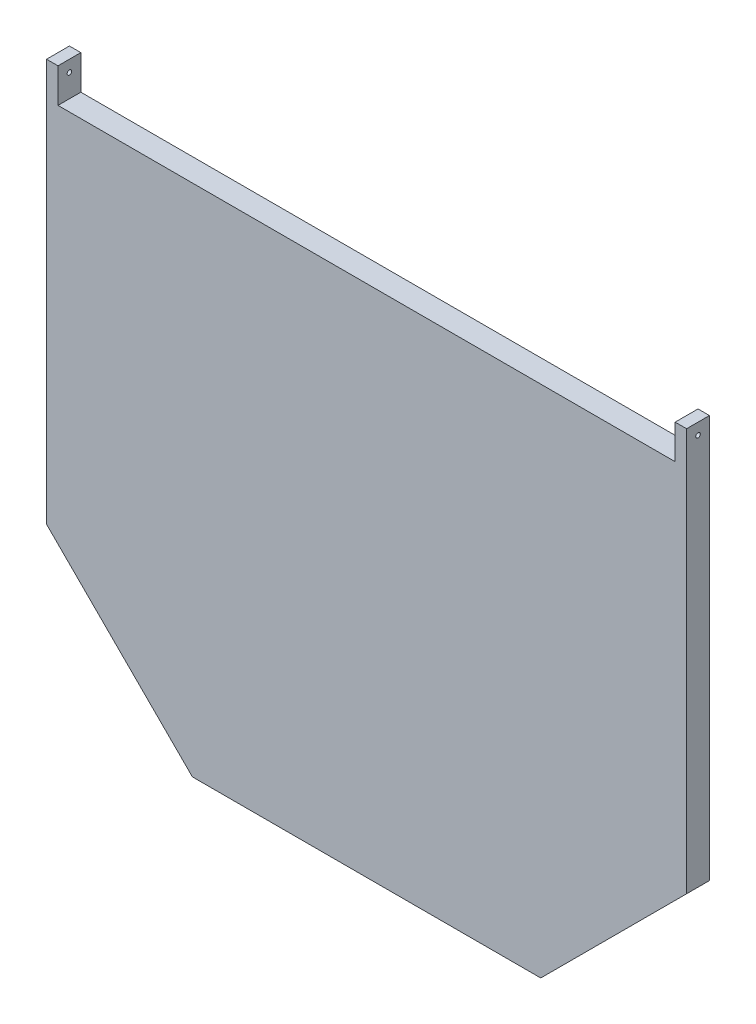
SolidWorks part; units mm, degrees
ref_plane "Front" through (0, 0, 0) normal (0, 0, 1) x (1, 0, 0)
ref_plane "Top" through (0, 0, 0) normal (0, 1, 0) x (1, 0, 0)
ref_plane "Right" through (0, 0, 0) normal (1, 0, 0) x (0, 0, -1)
sketch "Sketch1" plane through (0, 0, 0) normal (0, 0, 1) x (1, 0, 0)
  line L0 (355.6, 0) -> (355.6, -223.774)
  line L1 (0, 0) -> (355.6, 0)
  line L2 (0, 0) -> (0, -223.774)
  line L5 (355.6, -223.774) -> (274.574, -304.8)
  line L6 (274.574, -304.8) -> (81.026, -304.8)
  line L7 (81.026, -304.8) -> (0, -223.774)
  point P1 (0, 0)
extrude "Boss-Extrude1" add sketch "Sketch1" along normal blind 12.7
sketch "Sketch2" plane through (0, 0, 12.7) normal (0, 0, 1) x (1, 0, 0)
  line L0 (355.6, 0) -> (0, 0) construction
  line L1 (6.35, -19.05) -> (349.25, -19.05)
  line L2 (6.35, -19.05) -> (6.35, 0)
  line L3 (6.35, 0) -> (349.25, 0)
  line L4 (349.25, -19.05) -> (349.25, 0)
  dimension "D1" = 19.05
extrude "Cut-Extrude1" cut sketch "Sketch2" against normal through all
sketch "Sketch3" plane through (0, 0, 0) normal (-1, 0, 0) x (0, 0, 1)
  line L0 (12.7, 0) -> (12.7, -223.774) construction
  line L1 (12.7, 0) -> (0, 0) construction
  circle A0 centre (6.35, -6.35) radius 1.27
  point P2 (0, 0)
  point P5 (0, 0)
  dimension "D1" = 2.54
  dimension "D2" = 6.35
  dimension "D3" = 6.35
extrude "Cut-Extrude2" cut sketch "Sketch3" against normal through all
